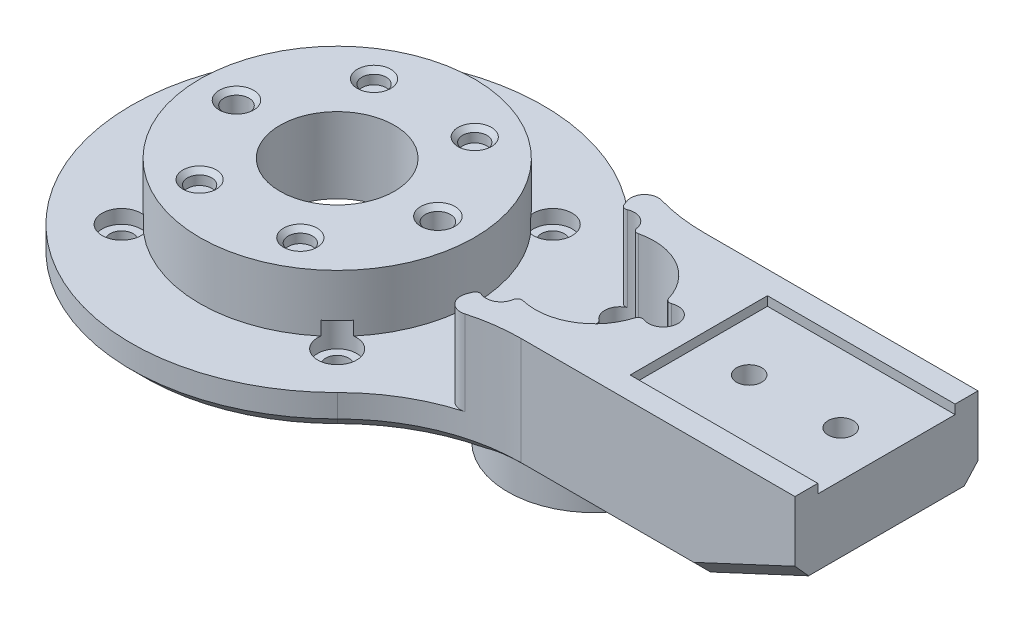
SolidWorks part; units mm, degrees
ref_plane "Front Plane" through (0, 0, 0) normal (0, 0, 1) x (1, 0, 0)
ref_plane "Top Plane" through (0, 0, 0) normal (0, 1, 0) x (1, 0, 0)
ref_plane "Right Plane" through (0, 0, 0) normal (1, 0, 0) x (0, 0, -1)
sketch "Sketch1" plane through (0, 0, 0) normal (0, 1, 0) x (1, 0, 0)
  circle A0 centre (0, 0) radius 30
  dimension "D1" = 60
extrude "Boss-Extrude1" add sketch "Sketch1" along normal blind 12.5
sketch "Sketch3" plane through (0, 0, 0) normal (0, -1, 0) x (1, 0, 0)
  line L1 (-28.2, -28.2) -> (28.2, -28.2) construction
  line L2 (-28.2, -28.2) -> (-28.2, 28.2) construction
  line L3 (-28.2, 28.2) -> (28.2, 28.2) construction
  line L4 (28.2, -28.2) -> (28.2, 28.2) construction
  line L5 (-28.2, -28.2) -> (28.2, 28.2) construction
  line L6 (-28.2, 28.2) -> (28.2, -28.2) construction
  circle A0 centre (0, 0) radius 45
  point P0 (0, 0)
  dimension "D2" = 90
  dimension "D1" = 56.4
extrude "Boss-Extrude3" add sketch "Sketch3" along normal blind 8
sketch "Sketch4" plane through (0, -8, 0) normal (0, -1, 0) x (1, 0, 0)
  line L1 (-23.5, -28.5) -> (23.5, -28.5)
  line L2 (-28.5, -23.5) -> (-28.5, 23.5)
  line L3 (-23.5, 28.5) -> (23.5, 28.5)
  line L4 (28.5, -23.5) -> (28.5, 23.5)
  line L5 (-28.5, -28.5) -> (28.5, 28.5) construction
  line L6 (-28.5, 28.5) -> (28.5, -28.5) construction
  arc A0 (-28.5, -23.5) -> (-23.5, -28.5) centre (-23.5, -23.5) ccw
  arc A1 (23.5, -28.5) -> (28.5, -23.5) centre (23.5, -23.5) ccw
  arc A2 (28.5, 23.5) -> (23.5, 28.5) centre (23.5, 23.5) ccw
  arc A3 (-23.5, 28.5) -> (-28.5, 23.5) centre (-23.5, 23.5) ccw
  point P0 (0, 0)
  dimension "D2" = 5
  dimension "D1" = 57
extrude "Cut-Extrude1" cut sketch "Sketch4" against normal blind 2
sketch "Sketch5" plane through (0, -6, 0) normal (0, -1, 0) x (1, 0, 0)
  circle A0 centre (0, 0) radius 19.5
  dimension "D1" = 39
extrude "Cut-Extrude2" cut sketch "Sketch5" against normal blind 2
sketch "Sketch6" plane through (0, -6, 0) normal (0, -1, 0) x (1, 0, 0)
  line L1 (-23.55, -23.55) -> (23.55, -23.55) construction
  line L2 (-23.55, -23.55) -> (-23.55, 23.55) construction
  line L3 (-23.55, 23.55) -> (23.55, 23.55) construction
  line L4 (23.55, -23.55) -> (23.55, 23.55) construction
  line L5 (-23.55, -23.55) -> (23.55, 23.55) construction
  line L6 (-23.55, 23.55) -> (23.55, -23.55) construction
  circle A0 centre (-23.55, 23.55) radius 2.5
  circle A1 centre (23.55, 23.55) radius 2.5
  circle A2 centre (23.55, -23.55) radius 2.5
  circle A3 centre (-23.55, -23.55) radius 2.5
  point P0 (0, 0)
  dimension "D2" = 5
  dimension "D1" = 47.1
extrude "Cut-Extrude3" cut sketch "Sketch6" against normal through all
sketch "Sketch8" plane through (0, 12.5, 0) normal (0, 1, 0) x (1, 0, 0)
  circle A0 centre (0, 0) radius 12.5
  dimension "D1" = 25
extrude "Cut-Extrude4" cut sketch "Sketch8" against normal through all
sketch "Sketch9" plane through (0, 12.5, 0) normal (0, 1, 0) x (1, 0, 0)
  circle A0 centre (-22, 0) radius 2.65
  circle A1 centre (-11, 19.0526) radius 2.65
  circle A2 centre (11, 19.0526) radius 2.65
  circle A3 centre (22, 0) radius 2.65
  circle A4 centre (11, -19.0526) radius 2.65
  circle A5 centre (-11, -19.0526) radius 2.65
  point P15 (0, 0)
  dimension "D2" = 5.3
  dimension "D1" = 22
  dimension "D3" = 6
sketch "Sketch12" plane through (0, 0, 0) normal (0, 1, 0) x (1, 0, 0)
  circle A0 centre (-23.55, 23.55) radius 4.25
  circle A1 centre (23.55, 23.55) radius 4.25
  circle A2 centre (23.55, -23.55) radius 4.25
  circle A3 centre (-23.55, -23.55) radius 4.25
  dimension "D1" = 8.5
extrude "Cut-Extrude7" cut sketch "Sketch12" against normal blind 3
sketch "Sketch17" plane through (0, 12.5, 0) normal (0, 1, 0) x (1, 0, 0)
  circle A0 centre (0, 0) radius 22 construction
  circle A6 centre (22, 0) radius 2.75
  circle A12 centre (-22, 0) radius 2.75
  dimension "D3" = 5.5
  dimension "D6" = 44
extrude "Cut-Extrude11" cut sketch "Sketch9" against normal blind 3 contours A4 | A2 | A1 | A5 region at (-11, 12.5, -19.0526) region at (11, 12.5, -19.0526) region at (11, 12.5, 19.0526)
sketch "Sketch19" plane through (0, -8, 0) normal (0, -1, 0) x (1, 0, 0)
  line L0 (45, 0) -> (120, 0) construction
  line L1 (40.3113, -20) -> (120, -20)
  line L2 (40.3113, 20) -> (120, 20)
  line L3 (120, 20) -> (120, -20)
  line L4 (0, 20) -> (120, 20) construction
  line L5 (0, 0) -> (120, 0) construction
  line L6 (0, -20) -> (120, -20) construction
  circle A0 centre (0, 0) radius 45 construction
  arc A1 (40.3113, -20) -> (40.3113, 20) centre (0, 0) ccw
  dimension "D3" = 120
  dimension "D1" = 20
  dimension "D2" = 20
extrude "Boss-Extrude4" add sketch "Sketch19" against normal up to surface (8 mm away) up to face at (0, 0, 0)
sketch "Sketch20" plane through (0, 0, 0) normal (0, 1, 0) x (1, 0, 0)
  line L0 (0, 0) -> (119.1554, 0) construction
  line L6 (44.7325, -20) -> (120, -20)
  line L7 (120, -20) -> (120, 20)
  line L8 (120, 20) -> (44.7325, 20)
  arc A0 (44.7325, -20) -> (44.7325, 20) centre (0, 0) ccw
  dimension "D1" = 98
  dimension "D2" = 40
  dimension "D3" = 120
extrude "Boss-Extrude5" add sketch "Sketch20" along normal blind 18.5
chamfer "Chamfer1" distance 10 angle 65 1 edges at (120, -8, 0) first distance on face at (120, 5.25, 0)
fillet "Fillet1" radius 40 2 edges at (40.3113, -4, -20) (40.3113, -4, 20)
sketch "Sketch21" plane through (0, -8, 0) normal (0, -1, 0) x (1, 0, 0)
  line L0 (120, 0) -> (0, 0) construction
  line L2 (120, 20) -> (120, -20) construction
  circle A0 centre (0, 0) radius 45.75 construction
  circle A1 centre (56.25, 0) radius 10.5 construction
  circle A2 centre (56.25, 0) radius 13
  dimension "D1" = 91.5
  dimension "D2" = 21
  dimension "D3" = 26
extrude "Cut-Extrude12" cut sketch "Sketch21" against normal blind 66
sketch "Sketch22" plane through (0, -8, 0) normal (0, -1, 0) x (1, 0, 0)
  circle A0 centre (56.25, 0) radius 19
  dimension "D1" = 38
extrude "Boss-Extrude6" add sketch "Sketch22" along normal blind 5
sketch "Sketch24" plane through (0, -8, 0) normal (0, -1, 0) x (1, 0, 0)
  circle A1 centre (56.25, 0) radius 13
  circle A2 centre (56.25, 0) radius 13
  dimension "D1" = 0
extrude "Cut-Extrude13" cut sketch "Sketch24" along normal blind 22
sketch "Sketch25" plane through (120, 0, 0) normal (1, 0, 0) x (0, 0, -1)
  line L0 (-20, 18.5) -> (20, 18.5) construction
  line L1 (15, 20.5) -> (-15, 20.5)
  line L2 (15, 20.5) -> (15, 16.5)
  line L3 (15, 16.5) -> (-15, 16.5)
  line L4 (-15, 20.5) -> (-15, 16.5)
  line L5 (15, 20.5) -> (-15, 16.5) construction
  line L6 (15, 16.5) -> (-15, 20.5) construction
  point P0 (0, 18.5)
  dimension "D1" = 4
  dimension "D2" = 30
extrude "Cut-Extrude14" cut sketch "Sketch25" against normal blind 41
sketch "Sketch26" plane through (0, -8, 0) normal (0, -1, 0) x (1, 0, 0)
  line L0 (120, 0) -> (0, 0) construction
  line L1 (120, 20) -> (120, -20) construction
  circle A0 centre (110, 0) radius 2.75
  circle A1 centre (90, 0) radius 2.75
  dimension "D3" = 5.5
  dimension "D1" = 10
  dimension "D2" = 20
extrude "Cut-Extrude15" cut sketch "Sketch26" against normal through all
sketch "Sketch27" plane through (0, -8, 0) normal (0, -1, 0) x (1, 0, 0)
  circle A0 centre (90, 0) radius 4.6
  circle A1 centre (110, 0) radius 4.6
  dimension "D1" = 9.2
extrude "Cut-Extrude16" cut sketch "Sketch27" against normal blind 12
chamfer "Chamfer3" distance 3 angle 45 7 edges at (109.2775, -3, -20) (79.3815, -8, -20) (44.8687, -8, -23.0581) (-45, -8, 0) (44.8687, -8, 23.0581) (109.2775, -3, 20) (79.3815, -8, 20)
sketch "Sketch43" plane through (0, -13, 0) normal (0, -1, 0) x (1, 0, 0)
  line L0 (56.25, 0) -> (71.25, -0.0026) construction
  line L1 (56.25, 0) -> (48.748, -12.9892) construction
  line L2 (56.25, 0) -> (48.7522, 12.9917) construction
  circle A0 centre (71.25, -0.0026) radius 1.75
  circle A1 centre (48.748, -12.9892) radius 1.75
  circle A2 centre (48.7522, 12.9917) radius 1.75
  circle A3 centre (56.25, 0) radius 15 construction
  dimension "D1" = 3.5
  dimension "D2" = 30
  dimension "D3" = 120.001
  dimension "D4" = 120
extrude "Cut-Extrude22" cut sketch "Sketch43" against normal blind 42
sketch "Sketch44" plane through (0, 0, 0) normal (0, 1, 0) x (1, 0, 0)
  circle A0 centre (48.7522, -12.9917) radius 3
  dimension "D1" = 6
extrude "Cut-Extrude23" cut sketch "Sketch44" against normal blind 8
extrude "Cut-Extrude25" cut sketch "Sketch17" against normal through all
sketch "Sketch47" plane through (0, -6, 0) normal (0, -1, 0) x (1, 0, 0)
  line L1 (-26.25, 2.4537) -> (-26.25, -2.4537)
  line L2 (-26.25, -2.4537) -> (-22, -4.9075)
  line L3 (-22, -4.9075) -> (-17.75, -2.4537)
  line L4 (-17.75, -2.4537) -> (-17.75, 2.4537)
  line L5 (-17.75, 2.4537) -> (-22, 4.9075)
  line L6 (-22, 4.9075) -> (-26.25, 2.4537)
  line L7 (17.75, 2.4537) -> (17.75, -2.4537)
  line L8 (17.75, -2.4537) -> (22, -4.9075)
  line L9 (22, -4.9075) -> (26.25, -2.4537)
  line L10 (26.25, -2.4537) -> (26.25, 2.4537)
  line L11 (26.25, 2.4537) -> (22, 4.9075)
  line L12 (22, 4.9075) -> (17.75, 2.4537)
  circle A0 centre (-22, 0) radius 4.25 construction
  circle A1 centre (22, 0) radius 4.25 construction
  point P10 (22, -4.25)
  point P19 (-22, -4.9067)
  point P20 (22, -4.9075)
  dimension "D1" = 8.5
extrude "Cut-Extrude26" cut sketch "Sketch47" against normal blind 12
sketch "Sketch48" plane through (0, 0, 0) normal (0, 1, 0) x (1, 0, 0)
  arc A0 (-19.3456, -22.9292) -> (-22.9292, -19.3456) centre (-23.55, -23.55) ccw construction
  arc A1 (-22.9292, -19.3456) -> (-19.3456, -22.9292) centre (-23.55, -23.55) ccw construction
  circle A2 centre (23.55, -23.55) radius 4.25 construction
  circle A3 centre (-23.55, 23.55) radius 4.25 construction
  circle A4 centre (23.55, 23.55) radius 4.25 construction
  arc A5 (-19.3456, -22.9292) -> (-22.9292, -19.3456) centre (-23.55, -23.55) ccw
  arc A6 (-22.9292, -19.3456) -> (-19.3456, -22.9292) centre (-23.55, -23.55) ccw
  circle A7 centre (23.55, -23.55) radius 4.25
  circle A8 centre (-23.55, 23.55) radius 4.25
  circle A9 centre (23.55, 23.55) radius 4.25
extrude "Cut-Extrude27" cut sketch "Sketch48" along normal blind 3
fillet "Fillet2" radius 3 2 edges at (42.7004, 9.25, 24.035) (42.7004, 9.25, -24.035)
sketch "Sketch49" plane through (0, 18.5, 0) normal (0, 1, 0) x (1, 0, 0)
  circle A0 centre (48.748, 12.9892) radius 3.25
  circle A1 centre (71.25, 0.0026) radius 3.25
  circle A2 centre (48.7522, -12.9917) radius 3.25
  dimension "D1" = 6.5
extrude "Cut-Extrude28" cut sketch "Sketch49" against normal blind 23
fillet "Fillet3" radius 1 6 edges at (47.8012, -2.25, -9.8802) (51.9141, 7, -12.2556) (51.9181, 7, 12.257) (47.8044, -2.25, 9.8829) (46.5294, 9.25, 15.3627) (46.5291, 9.25, -15.3638)
fillet "Fillet4" radius 1 2 edges at (69.0317, 7, 2.3726) (69.0308, 7, -2.377)
chamfer "Chamfer4" distance 1 angle 45 2 edges at (22, 12.5, 2.75) (-22, 12.5, 2.75)
chamfer "Chamfer5" distance 1 angle 45 4 edges at (-11, 12.5, -16.4026) (11, 12.5, -16.4026) (11, 12.5, 21.7026) (-11, 12.5, 21.7026)
chamfer "Chamfer6" distance 1 angle 45 3 edges at (48.7522, -8, 14.7417) (71.25, -4.5, 1.7474) (48.748, -4.5, -11.2392)
sketch "Sketch52" plane through (0, 18.5, 0) normal (0, 1, 0) x (1, 0, 0)
  circle A1 centre (0, 0) radius 49
  dimension "D1" = 98
